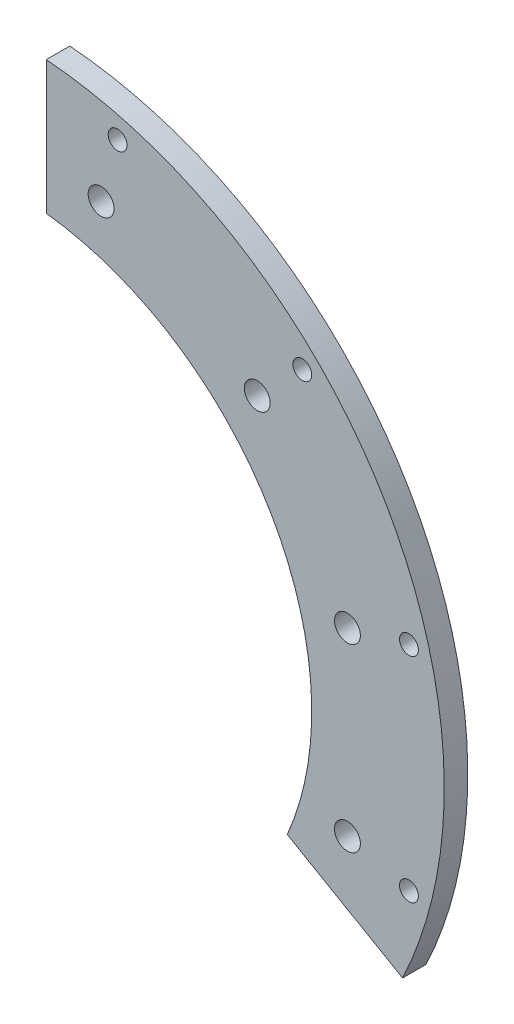
SolidWorks part; units mm, degrees
material "Teck"
ref_plane "Plan de face" through (0, 0, 0) normal (0, 0, 1) x (1, 0, 0)
ref_plane "Plan de dessus" through (0, 0, 0) normal (0, 1, 0) x (1, 0, 0)
ref_plane "Plan de droite" through (0, 0, 0) normal (1, 0, 0) x (0, 0, -1)
sketch "Esquisse1" plane through (0, 0, 0) normal (0, 0, 1) x (1, 0, 0)
  line L0 (6, 73.3651) -> (6, 50.7465)
  line L1 (66.5339, -31.4909) -> (46.9458, -20.1817)
  line L2 (0, 73.61) -> (0, 0) construction
  line L3 (0, 0) -> (63.7481, -36.805) construction
  arc A0 (6, 50.7465) -> (46.9458, -20.1817) centre (0, 0) cw
  arc A2 (6, 73.3651) -> (66.5339, -31.4909) centre (0, 0) cw
  circle A3 centre (0, 0) radius 73.61 construction
  point P1 (0, 0)
  point P4 (0, 0)
  dimension "D4" = 73.61
  dimension "D5" = 51.1
  dimension "D1" = 120
  dimension "D2" = 6
  dimension "D3" = 6
extrude "Boss.-Extru.1" add sketch "Esquisse1" along normal blind 4 contours L0 A0 L1 A2
sketch "Sketch2" plane through (0, 0, 4) normal (0, 0, 1) x (1, 0, 0)
  line L0 (0, 0) -> (0, 96.9743) construction
  line L1 (0, 0) -> (18.1173, 67.6148) construction
  line L2 (18.1173, 67.6148) -> (29.3318, 109.4676) construction
  circle A0 centre (18.1173, 67.6148) radius 1.6
  circle A1 centre (15.3169, 57.1635) radius 2.2
  point P7 (35.0097, 96.9743)
  dimension "D2" = 3.2
  dimension "D4" = 4.4
  dimension "D1" = 70
  dimension "D3" = 59.18
  dimension "D5" = 15
extrude "Cut-Extrude1" cut sketch "Sketch2" against normal through all
ref_axis "Axis1" through (0, 0, -0.2) along (0, 0, 1)
pattern_circular "CirPattern1" count 12 over 360 about axis through (0, 0, -0.2) along (0, 0, 1) of "Cut-Extrude1" reverse direction yes
